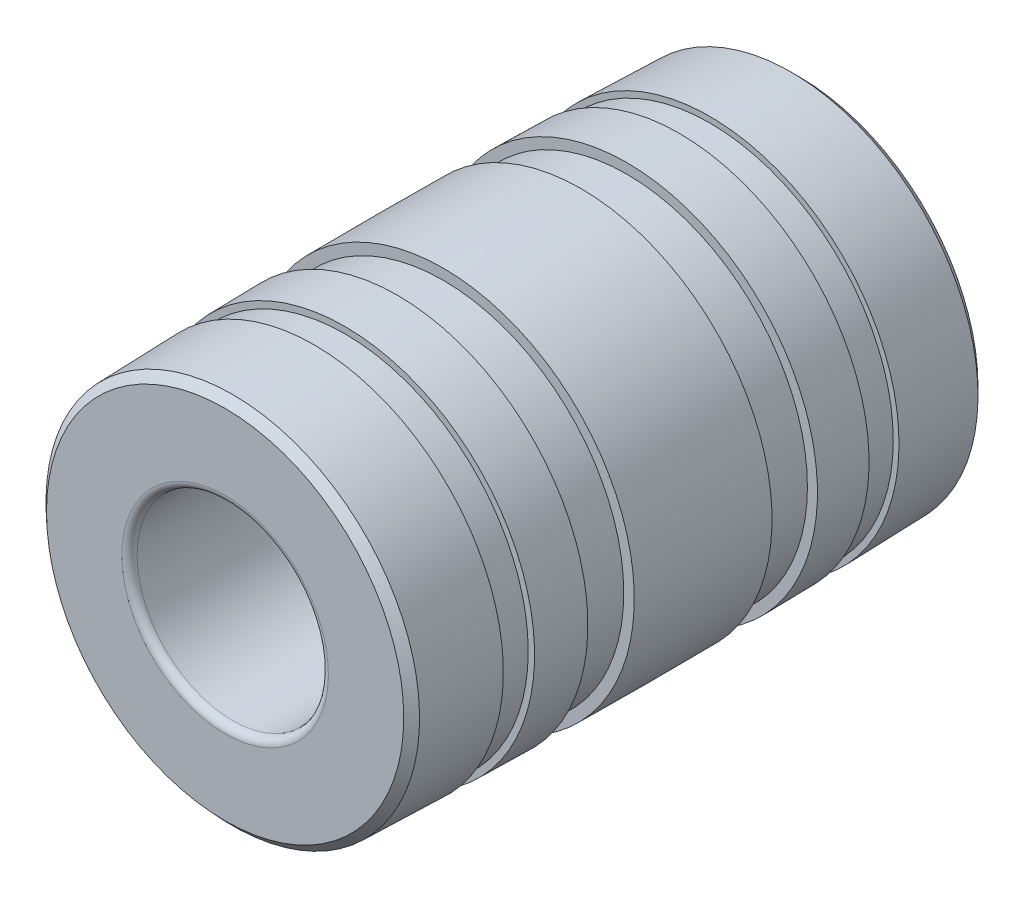
SolidWorks part; units mm, degrees
ref_plane "Front" through (0, 0, 0) normal (0, 0, 1) x (1, 0, 0)
ref_plane "Top" through (0, 0, 0) normal (0, 1, 0) x (1, 0, 0)
ref_plane "Right" through (0, 0, 0) normal (1, 0, 0) x (0, 0, -1)
sketch "Sketch1" plane through (0, 0, 0) normal (1, 0, 0) x (0, 0, -1)
  line L0 (-9.525, 0) -> (9.525, 0)
  line L1 (-9.525, 0) -> (-9.525, -6.1912)
  line L2 (0, 0) -> (0, -6.35) construction
  line L3 (-9.525, -6.1912) -> (-9.525, 6.1913) construction
  line L4 (-6.5659, -6.2746) -> (-6.5659, -6.0841)
  line L5 (-6.5659, -6.0841) -> (-5.5499, -6.0841)
  line L6 (-5.5499, -6.0841) -> (-5.5499, -6.2961)
  line L7 (-9.525, -6.35) -> (-9.525, 6.35) construction
  line L8 (6.5659, -6.0841) -> (9.525, -6.0841) construction
  line L9 (9.525, -6.0841) -> (9.525, 6.0841) construction
  line L10 (9.525, 0) -> (9.525, -6.1912)
  line L11 (-5.5499, -6.35) -> (5.5499, -6.35) construction
  line L12 (-3.81, -6.3246) -> (-3.81, -5.9912)
  line L13 (-3.81, -5.9912) -> (-2.286, -5.9912)
  line L14 (-2.286, -5.9912) -> (-2.286, -6.3409)
  line L15 (-2.286, -5.9912) -> (0, -5.9912) construction
  line L16 (5.5499, -6.0841) -> (5.5499, -6.2961)
  line L17 (6.5659, -6.0841) -> (5.5499, -6.0841)
  line L18 (6.5659, -6.2746) -> (6.5659, -6.0841)
  line L19 (0, -5.9912) -> (2.286, -5.9912) construction
  line L20 (-5.5499, -6.0841) -> (-3.81, -6.0841) construction
  line L21 (5.5499, -6.0841) -> (3.81, -6.0841) construction
  line L22 (2.286, -6.3409) -> (2.286, -5.9912)
  line L23 (2.286, -5.9912) -> (3.81, -5.9912)
  line L24 (3.81, -5.9912) -> (3.81, -6.3246)
  line L25 (-6.5659, -6.2746) -> (6.5659, -6.2746) construction
  arc A0 (0, -6.35) -> (-2.286, -6.3409) centre (0, 279.4794) cw
  arc A1 (0, -6.35) -> (2.286, -6.3409) centre (0, 279.4794) ccw
  arc A2 (-3.81, -6.3246) -> (-5.5499, -6.2961) centre (0, 279.4794) cw
  arc A3 (-6.5659, -6.2746) -> (-9.525, -6.1912) centre (0, 279.4794) cw
  arc A4 (3.81, -6.3246) -> (5.5499, -6.2961) centre (0, 279.4794) ccw
  arc A5 (6.5659, -6.2746) -> (9.525, -6.1912) centre (0, 279.4794) ccw
  point P13 (9.525, 6.35)
  dimension "D1" = 1.524
  dimension "Overall Lg B" = 19.05
  dimension "D2" = 0.1905
  dimension "D3" = 0.3334
  dimension "D4" = 12.3825
  dimension "D5" = 1.016
  dimension "Lg C" = 13.1318
  dimension "OD A" = 12.7
  dimension "Supplier D Between Retaining Rings" = 11.0998
  dimension "Supplier E Between O-Rings" = 4.572
revolve "Bearing" add sketch "Sketch1" angle 360 about L0
sketch "Sketch2" plane through (0, 0, 0) normal (0, 0, 1) x (1, 0, 0)
  circle A0 centre (0, 0) radius 3.175
  circle A1 centre (0, 0) radius 6.35 construction
  dimension "For Shaft Dia" = 6.35
extrude "Bore" cut sketch "Sketch2" against normal through all and the other way through all
chamfer "OD Chamfer" distance 0.254 angle 45 2 edges at (0, -6.1913, -9.525) (0, -6.1912, 9.525) first distance on face at (3.175, 0, -9.525) first distance on face at (0, -6.2746, 6.5659)
fillet "ID Fillet" radius 0.254 2 edges at (3.175, 0, -9.525) (3.175, 0, 9.525)
sketch "Retaining Hole" [suppressed] plane through (0, 0, 0) normal (1, 0, 0) x (0, 0, -1)
  line L0 (-9.525, -6.1912) -> (-9.525, 6.1913) construction
  line L1 (-9.525, 0) -> (9.525, 0) construction
  circle A0 centre (0, 0) radius 1.1938
  dimension "Supplier H Hole Dia" = 2.3876
  dimension "Supplier I Hole Locate" = 9.525
extrude "Retaining Hole " [suppressed] cut sketch "Retaining Hole" along normal through all
sketch "Slot Opening" [suppressed] plane through (0, 0, 0) normal (0, 0, 1) x (1, 0, 0)
  line L0 (0, -38.1) -> (0, -3.2029) construction
  line L1 (-12.7, -21.997) -> (12.7, -21.997)
  line L2 (-12.7, -21.997) -> (-21.997, -38.1)
  line L3 (-21.997, -38.1) -> (21.997, -38.1)
  line L4 (21.997, -38.1) -> (12.7, -21.997)
  circle A2 centre (0, 0) radius 25.4 construction
  dimension "D1" = 60
  dimension "Wd E" = 3.175
extrude "Slot Opening " [suppressed] cut sketch "Slot Opening" against normal through all and the other way through all
other "Move Face1" [suppressed] offset 3.175 parameters "D1"=3.175
other "Move Face2" [suppressed] flip direction yes parameters "D1"=15
sketch "Ref" [suppressed] plane through (0, 0, 0) normal (0, 0, 1) x (1, 0, 0)
  line L0 (13.0254, 5.2388) -> (7.0543, 3.6389) construction
  line L1 (13.2667, 5.3035) -> (7.0543, 3.6389) construction
  line L2 (7.9286, 0.3758) -> (13.8998, 1.9757) construction
  line L3 (7.9286, 0.3758) -> (14.1411, 2.0404) construction
  line L4 (7.667, 2.0544) -> (13.8007, 3.6979) construction
  line L5 (0, 0) -> (14.2875, 0) construction
  circle A0 centre (0, 0) radius 14.2875 construction
  arc A1 (14.1411, 2.0404) -> (13.2667, 5.3035) centre (0, 0) ccw construction
  circle A2 centre (0, 0) radius 7.9375 construction
  arc A3 (7.9286, 0.3758) -> (7.0543, 3.6389) centre (0, 0) ccw construction
equation "\"D1@Sketch1\" = \"D5@Sketch1\" * 1.5"
equation "\"D4@Sketch1\" = \"OD A@Sketch1\" * .975"
equation "\"D2@Sketch1\" = \"OD A@Sketch1\" * .015"
equation "\"D3@Sketch1\" = \"D2@Sketch1\" * 1.75"
